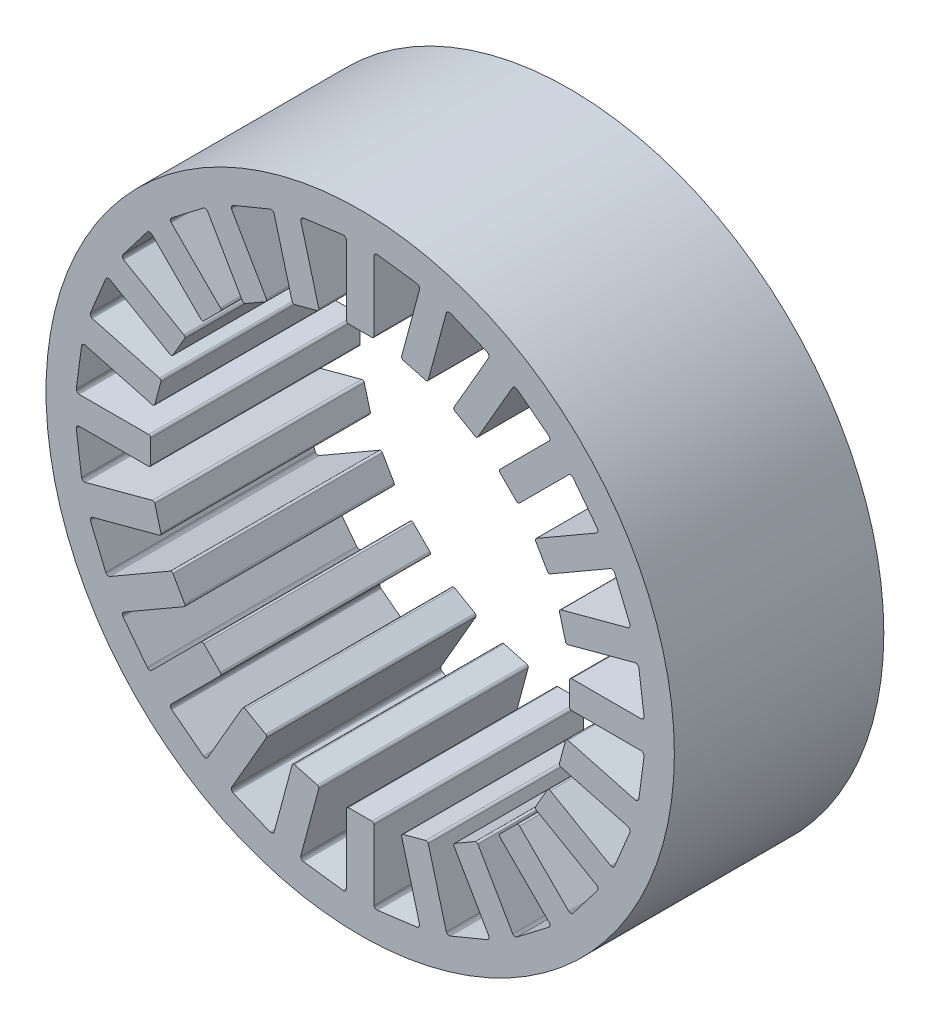
SolidWorks part; units mm, degrees
ref_plane "Ön Düzlem" through (0, 0, 0) normal (0, 0, 1) x (1, 0, 0)
ref_plane "Üst Düzlem" through (0, 0, 0) normal (0, 1, 0) x (1, 0, 0)
ref_plane "Sağ Düzlem" through (0, 0, 0) normal (1, 0, 0) x (0, 0, -1)
sketch "Model" plane through (0, 0, 0) normal (0, 0, 1) x (1, 0, 0)
  line L1 (60.5945, 121.4987) -> (60.8885, 121.3363)
  line L2 (60.8885, 121.3363) -> (61.139, 121.1124)
  line L3 (61.139, 121.1124) -> (61.3334, 120.8385)
  line L4 (61.3334, 120.8385) -> (61.4619, 120.5282)
  line L5 (61.4619, 120.5282) -> (61.5182, 120.197)
  line L6 (61.5182, 120.197) -> (61.4993, 119.8617)
  line L7 (61.4993, 119.8617) -> (61.4063, 119.5389)
  line L8 (61.4063, 119.5389) -> (45.7726, 92.4605)
  line L9 (45.7726, 92.4605) -> (42.0525, 92.3778)
  line L10 (42.0525, 92.3778) -> (41.4785, 90.992)
  line L11 (58.0621, 81.4174) -> (58.9753, 82.6074)
  line L12 (58.9753, 82.6074) -> (57.1868, 85.8705)
  line L13 (57.1868, 85.8705) -> (72.8206, 112.9489)
  line L14 (72.8206, 112.9489) -> (73.0536, 113.1908)
  line L15 (73.0536, 113.1908) -> (73.3346, 113.3748)
  line L16 (73.3346, 113.3748) -> (73.6495, 113.4917)
  line L17 (73.6495, 113.4917) -> (73.9825, 113.5355)
  line L18 (73.9825, 113.5355) -> (74.317, 113.5041)
  line L19 (74.317, 113.5041) -> (74.636, 113.3991)
  line L20 (74.636, 113.3991) -> (74.9237, 113.2258)
  line L21 (74.9237, 113.2258) -> (89.976, 101.6758)
  line L22 (89.976, 101.6758) -> (90.2179, 101.4427)
  line L23 (90.2179, 101.4427) -> (90.4019, 101.1617)
  line L24 (90.4019, 101.1617) -> (90.5188, 100.8468)
  line L25 (90.5188, 100.8468) -> (90.5626, 100.5138)
  line L26 (90.5626, 100.5138) -> (90.5313, 100.1793)
  line L27 (90.5313, 100.1793) -> (90.4263, 99.8603)
  line L28 (90.4263, 99.8603) -> (90.2529, 99.5726)
  line L29 (90.2529, 99.5726) -> (68.1435, 77.4631)
  line L30 (68.1435, 77.4631) -> (64.5287, 78.3461)
  line L31 (64.5287, 78.3461) -> (63.6156, 77.1561)
  line L32 (77.1561, 63.6156) -> (78.3461, 64.5287)
  line L33 (78.3461, 64.5287) -> (77.4631, 68.1435)
  line L34 (77.4631, 68.1435) -> (99.5726, 90.2529)
  line L35 (99.5726, 90.2529) -> (99.8603, 90.4263)
  line L36 (99.8603, 90.4263) -> (100.1793, 90.5313)
  line L37 (100.1793, 90.5313) -> (100.5138, 90.5626)
  line L38 (100.5138, 90.5626) -> (100.8468, 90.5188)
  line L39 (100.8468, 90.5188) -> (101.1617, 90.4019)
  line L40 (101.1617, 90.4019) -> (101.4427, 90.2179)
  line L41 (101.4427, 90.2179) -> (101.6758, 89.976)
  line L42 (101.6758, 89.976) -> (113.2258, 74.9237)
  line L43 (113.2258, 74.9237) -> (113.3991, 74.636)
  line L44 (113.3991, 74.636) -> (113.5041, 74.317)
  line L45 (113.5041, 74.317) -> (113.5355, 73.9825)
  line L46 (113.5355, 73.9825) -> (113.4917, 73.6495)
  line L47 (113.4917, 73.6495) -> (113.3748, 73.3346)
  line L48 (113.3748, 73.3346) -> (113.1908, 73.0536)
  line L49 (113.1908, 73.0536) -> (112.9489, 72.8206)
  line L50 (112.9489, 72.8206) -> (85.8705, 57.1868)
  line L51 (85.8705, 57.1868) -> (82.6074, 58.9753)
  line L52 (82.6074, 58.9753) -> (81.4174, 58.0621)
  line L53 (90.992, 41.4785) -> (92.3778, 42.0525)
  line L54 (92.3778, 42.0525) -> (92.4605, 45.7726)
  line L55 (92.4605, 45.7726) -> (119.5389, 61.4063)
  line L56 (119.5389, 61.4063) -> (119.8617, 61.4993)
  line L57 (119.8617, 61.4993) -> (120.197, 61.5182)
  line L58 (120.197, 61.5182) -> (120.5282, 61.4619)
  line L59 (120.5282, 61.4619) -> (120.8385, 61.3334)
  line L60 (120.8385, 61.3334) -> (121.1124, 61.139)
  line L61 (121.1124, 61.139) -> (121.3363, 60.8885)
  line L62 (121.3363, 60.8885) -> (121.4987, 60.5945)
  line L63 (121.4987, 60.5945) -> (128.7594, 43.0658)
  line L64 (128.7594, 43.0658) -> (128.8524, 42.743)
  line L65 (128.8524, 42.743) -> (128.8712, 42.4076)
  line L66 (128.8712, 42.4076) -> (128.815, 42.0765)
  line L67 (128.815, 42.0765) -> (128.6864, 41.7662)
  line L68 (128.6864, 41.7662) -> (128.492, 41.4922)
  line L69 (128.492, 41.4922) -> (128.2416, 41.2684)
  line L70 (128.2416, 41.2684) -> (127.9476, 41.1059)
  line L71 (127.9476, 41.1059) -> (97.7455, 33.0133)
  line L72 (97.7455, 33.0133) -> (95.0566, 35.5853)
  line L73 (95.0566, 35.5853) -> (93.6707, 35.0113)
  line L74 (98.6269, 16.5147) -> (100.1141, 16.7105)
  line L75 (100.1141, 16.7105) -> (101.1568, 20.2824)
  line L76 (101.1568, 20.2824) -> (131.3588, 28.375)
  line L77 (131.3588, 28.375) -> (131.6947, 28.3813)
  line L78 (131.6947, 28.3813) -> (132.0235, 28.3127)
  line L79 (132.0235, 28.3127) -> (132.3288, 28.1726)
  line L80 (132.3288, 28.1726) -> (132.5953, 27.9682)
  line L81 (132.5953, 27.9682) -> (132.8096, 27.7095)
  line L82 (132.8096, 27.7095) -> (132.9609, 27.4097)
  line L83 (132.9609, 27.4097) -> (133.0418, 27.0836)
  line L84 (133.0418, 27.0836) -> (135.5183, 8.273)
  line L85 (135.5183, 8.273) -> (135.5246, 7.9371)
  line L86 (135.5246, 7.9371) -> (135.4559, 7.6083)
  line L87 (135.4559, 7.6083) -> (135.3159, 7.303)
  line L88 (135.3159, 7.303) -> (135.1114, 7.0365)
  line L89 (135.1114, 7.0365) -> (134.8528, 6.8222)
  line L90 (134.8528, 6.8222) -> (134.5529, 6.6709)
  line L91 (134.5529, 6.6709) -> (134.2269, 6.59)
  line L92 (134.2269, 6.59) -> (102.9594, 6.59)
  line L93 (102.9594, 6.59) -> (101.0278, 9.7704)
  line L94 (101.0278, 9.7704) -> (99.5406, 9.5746)
  line L95 (99.5406, -9.5746) -> (101.0278, -9.7704)
  line L96 (101.0278, -9.7704) -> (102.9594, -6.59)
  line L97 (102.9594, -6.59) -> (134.2269, -6.59)
  line L98 (134.2269, -6.59) -> (134.5529, -6.6709)
  line L99 (134.5529, -6.6709) -> (134.8528, -6.8222)
  line L100 (134.8528, -6.8222) -> (135.1114, -7.0365)
  line L101 (135.1114, -7.0365) -> (135.3159, -7.303)
  line L102 (135.3159, -7.303) -> (135.4559, -7.6083)
  line L103 (135.4559, -7.6083) -> (135.5246, -7.9371)
  line L104 (135.5246, -7.9371) -> (135.5183, -8.273)
  line L105 (135.5183, -8.273) -> (133.0418, -27.0836)
  line L106 (133.0418, -27.0836) -> (132.9609, -27.4097)
  line L107 (132.9609, -27.4097) -> (132.8096, -27.7095)
  line L108 (132.8096, -27.7095) -> (132.5953, -27.9682)
  line L109 (132.5953, -27.9682) -> (132.3288, -28.1726)
  line L110 (132.3288, -28.1726) -> (132.0235, -28.3127)
  line L111 (132.0235, -28.3127) -> (131.6947, -28.3813)
  line L112 (131.6947, -28.3813) -> (131.3588, -28.375)
  line L113 (131.3588, -28.375) -> (101.1568, -20.2824)
  line L114 (101.1568, -20.2824) -> (100.1141, -16.7105)
  line L115 (100.1141, -16.7105) -> (98.6269, -16.5147)
  line L116 (93.6707, -35.0113) -> (95.0566, -35.5853)
  line L117 (95.0566, -35.5853) -> (97.7455, -33.0133)
  line L118 (97.7455, -33.0133) -> (127.9476, -41.1059)
  line L119 (127.9476, -41.1059) -> (128.2416, -41.2684)
  line L120 (128.2416, -41.2684) -> (128.492, -41.4922)
  line L121 (128.492, -41.4922) -> (128.6864, -41.7662)
  line L122 (128.6864, -41.7662) -> (128.815, -42.0765)
  line L123 (128.815, -42.0765) -> (128.8712, -42.4076)
  line L124 (128.8712, -42.4076) -> (128.8524, -42.743)
  line L125 (128.8524, -42.743) -> (128.7594, -43.0658)
  line L126 (128.7594, -43.0658) -> (121.4987, -60.5945)
  line L127 (121.4987, -60.5945) -> (121.3363, -60.8885)
  line L128 (121.3363, -60.8885) -> (121.1124, -61.139)
  line L129 (121.1124, -61.139) -> (120.8385, -61.3334)
  line L130 (120.8385, -61.3334) -> (120.5282, -61.4619)
  line L131 (120.5282, -61.4619) -> (120.197, -61.5182)
  line L132 (120.197, -61.5182) -> (119.8617, -61.4993)
  line L133 (119.8617, -61.4993) -> (119.5389, -61.4063)
  line L134 (119.5389, -61.4063) -> (92.4605, -45.7726)
  line L135 (92.4605, -45.7726) -> (92.3778, -42.0525)
  line L136 (92.3778, -42.0525) -> (90.992, -41.4785)
  line L137 (81.4174, -58.0621) -> (82.6074, -58.9753)
  line L138 (82.6074, -58.9753) -> (85.8705, -57.1868)
  line L139 (85.8705, -57.1868) -> (112.9489, -72.8206)
  line L140 (112.9489, -72.8206) -> (113.1908, -73.0536)
  line L141 (113.1908, -73.0536) -> (113.3748, -73.3346)
  line L142 (113.3748, -73.3346) -> (113.4917, -73.6495)
  line L143 (113.4917, -73.6495) -> (113.5355, -73.9825)
  line L144 (113.5355, -73.9825) -> (113.5041, -74.317)
  line L145 (113.5041, -74.317) -> (113.3991, -74.636)
  line L146 (113.3991, -74.636) -> (113.2258, -74.9237)
  line L147 (113.2258, -74.9237) -> (101.6758, -89.976)
  line L148 (101.6758, -89.976) -> (101.4427, -90.2179)
  line L149 (101.4427, -90.2179) -> (101.1617, -90.4019)
  line L150 (101.1617, -90.4019) -> (100.8468, -90.5188)
  line L151 (100.8468, -90.5188) -> (100.5138, -90.5626)
  line L152 (100.5138, -90.5626) -> (100.1793, -90.5313)
  line L153 (100.1793, -90.5313) -> (99.8603, -90.4263)
  line L154 (99.8603, -90.4263) -> (99.5726, -90.2529)
  line L155 (99.5726, -90.2529) -> (77.4631, -68.1435)
  line L156 (77.4631, -68.1435) -> (78.3461, -64.5287)
  line L157 (78.3461, -64.5287) -> (77.1561, -63.6156)
  line L158 (63.6156, -77.1561) -> (64.5287, -78.3461)
  line L159 (64.5287, -78.3461) -> (68.1435, -77.4631)
  line L160 (68.1435, -77.4631) -> (90.2529, -99.5726)
  line L161 (90.2529, -99.5726) -> (90.4263, -99.8603)
  line L162 (90.4263, -99.8603) -> (90.5313, -100.1793)
  line L163 (90.5313, -100.1793) -> (90.5626, -100.5138)
  line L164 (90.5626, -100.5138) -> (90.5188, -100.8468)
  line L165 (90.5188, -100.8468) -> (90.4019, -101.1617)
  line L166 (90.4019, -101.1617) -> (90.2179, -101.4427)
  line L167 (90.2179, -101.4427) -> (89.976, -101.6758)
  line L168 (89.976, -101.6758) -> (74.9237, -113.2258)
  line L169 (74.9237, -113.2258) -> (74.636, -113.3991)
  line L170 (74.636, -113.3991) -> (74.317, -113.5041)
  line L171 (74.317, -113.5041) -> (73.9825, -113.5355)
  line L172 (73.9825, -113.5355) -> (73.6495, -113.4917)
  line L173 (73.6495, -113.4917) -> (73.3346, -113.3748)
  line L174 (73.3346, -113.3748) -> (73.0536, -113.1908)
  line L175 (73.0536, -113.1908) -> (72.8206, -112.9489)
  line L176 (72.8206, -112.9489) -> (57.1868, -85.8705)
  line L177 (57.1868, -85.8705) -> (58.9753, -82.6074)
  line L178 (58.9753, -82.6074) -> (58.0621, -81.4174)
  line L179 (41.4785, -90.992) -> (42.0525, -92.3778)
  line L180 (42.0525, -92.3778) -> (45.7726, -92.4605)
  line L181 (45.7726, -92.4605) -> (61.4063, -119.5389)
  line L182 (61.4063, -119.5389) -> (61.4993, -119.8617)
  line L183 (61.4993, -119.8617) -> (61.5182, -120.197)
  line L184 (61.5182, -120.197) -> (61.4619, -120.5282)
  line L185 (61.4619, -120.5282) -> (61.3334, -120.8385)
  line L186 (61.3334, -120.8385) -> (61.139, -121.1124)
  line L187 (61.139, -121.1124) -> (60.8885, -121.3363)
  line L188 (60.8885, -121.3363) -> (60.5945, -121.4987)
  line L189 (60.5945, -121.4987) -> (43.0658, -128.7594)
  line L190 (43.0658, -128.7594) -> (42.743, -128.8524)
  line L191 (42.743, -128.8524) -> (42.4076, -128.8712)
  line L192 (42.4076, -128.8712) -> (42.0765, -128.815)
  line L193 (42.0765, -128.815) -> (41.7662, -128.6864)
  line L194 (41.7662, -128.6864) -> (41.4922, -128.492)
  line L195 (41.4922, -128.492) -> (41.2684, -128.2416)
  line L196 (41.2684, -128.2416) -> (41.1059, -127.9476)
  line L197 (41.1059, -127.9476) -> (33.0133, -97.7455)
  line L198 (33.0133, -97.7455) -> (35.5853, -95.0566)
  line L199 (35.5853, -95.0566) -> (35.0113, -93.6707)
  line L200 (16.5147, -98.6269) -> (16.7105, -100.1141)
  line L201 (16.7105, -100.1141) -> (20.2824, -101.1568)
  line L202 (20.2824, -101.1568) -> (28.375, -131.3588)
  line L203 (28.375, -131.3588) -> (28.3813, -131.6947)
  line L204 (28.3813, -131.6947) -> (28.3127, -132.0235)
  line L205 (28.3127, -132.0235) -> (28.1726, -132.3288)
  line L206 (28.1726, -132.3288) -> (27.9682, -132.5953)
  line L207 (27.9682, -132.5953) -> (27.7095, -132.8096)
  line L208 (27.7095, -132.8096) -> (27.4097, -132.9609)
  line L209 (27.4097, -132.9609) -> (27.0836, -133.0418)
  line L210 (27.0836, -133.0418) -> (8.273, -135.5183)
  line L211 (8.273, -135.5183) -> (7.9371, -135.5246)
  line L212 (7.9371, -135.5246) -> (7.6083, -135.4559)
  line L213 (7.6083, -135.4559) -> (7.303, -135.3159)
  line L214 (7.303, -135.3159) -> (7.0365, -135.1114)
  line L215 (7.0365, -135.1114) -> (6.8222, -134.8528)
  line L216 (6.8222, -134.8528) -> (6.6709, -134.5529)
  line L217 (6.6709, -134.5529) -> (6.59, -134.2269)
  line L218 (6.59, -134.2269) -> (6.59, -102.9594)
  line L219 (6.59, -102.9594) -> (9.7704, -101.0278)
  line L220 (9.7704, -101.0278) -> (9.5746, -99.5406)
  line L221 (-9.5746, -99.5406) -> (-9.7704, -101.0278)
  line L222 (-9.7704, -101.0278) -> (-6.59, -102.9594)
  line L223 (-6.59, -102.9594) -> (-6.59, -134.2269)
  line L224 (-6.59, -134.2269) -> (-6.6709, -134.5529)
  line L225 (-6.6709, -134.5529) -> (-6.8222, -134.8528)
  line L226 (-6.8222, -134.8528) -> (-7.0365, -135.1114)
  line L227 (-7.0365, -135.1114) -> (-7.303, -135.3159)
  line L228 (-7.303, -135.3159) -> (-7.6083, -135.4559)
  line L229 (-7.6083, -135.4559) -> (-7.9371, -135.5246)
  line L230 (-7.9371, -135.5246) -> (-8.273, -135.5183)
  line L231 (-8.273, -135.5183) -> (-27.0836, -133.0418)
  line L232 (-27.0836, -133.0418) -> (-27.4097, -132.9609)
  line L233 (-27.4097, -132.9609) -> (-27.7095, -132.8096)
  line L234 (-27.7095, -132.8096) -> (-27.9682, -132.5953)
  line L235 (-27.9682, -132.5953) -> (-28.1726, -132.3288)
  line L236 (-28.1726, -132.3288) -> (-28.3127, -132.0235)
  line L237 (-28.3127, -132.0235) -> (-28.3813, -131.6947)
  line L238 (-28.3813, -131.6947) -> (-28.375, -131.3588)
  line L239 (-28.375, -131.3588) -> (-20.2824, -101.1568)
  line L240 (-20.2824, -101.1568) -> (-16.7105, -100.1141)
  line L241 (-16.7105, -100.1141) -> (-16.5147, -98.6269)
  line L242 (-35.0113, -93.6707) -> (-35.5853, -95.0566)
  line L243 (-35.5853, -95.0566) -> (-33.0133, -97.7455)
  line L244 (-33.0133, -97.7455) -> (-41.1059, -127.9476)
  line L245 (-41.1059, -127.9476) -> (-41.2684, -128.2416)
  line L246 (-41.2684, -128.2416) -> (-41.4922, -128.492)
  line L247 (-41.4922, -128.492) -> (-41.7662, -128.6864)
  line L248 (-41.7662, -128.6864) -> (-42.0765, -128.815)
  line L249 (-42.0765, -128.815) -> (-42.4076, -128.8712)
  line L250 (-42.4076, -128.8712) -> (-42.743, -128.8524)
  line L251 (-42.743, -128.8524) -> (-43.0658, -128.7594)
  line L252 (-43.0658, -128.7594) -> (-60.5945, -121.4987)
  line L253 (-60.5945, -121.4987) -> (-60.8885, -121.3363)
  line L254 (-60.8885, -121.3363) -> (-61.139, -121.1124)
  line L255 (-61.139, -121.1124) -> (-61.3334, -120.8385)
  line L256 (-61.3334, -120.8385) -> (-61.4619, -120.5282)
  line L257 (-61.4619, -120.5282) -> (-61.5182, -120.197)
  line L258 (-61.5182, -120.197) -> (-61.4993, -119.8617)
  line L259 (-61.4993, -119.8617) -> (-61.4063, -119.5389)
  line L260 (-61.4063, -119.5389) -> (-45.7726, -92.4605)
  line L261 (-45.7726, -92.4605) -> (-42.0525, -92.3778)
  line L262 (-42.0525, -92.3778) -> (-41.4785, -90.992)
  line L263 (-58.0621, -81.4174) -> (-58.9753, -82.6074)
  line L264 (-58.9753, -82.6074) -> (-57.1868, -85.8705)
  line L265 (-57.1868, -85.8705) -> (-72.8206, -112.9489)
  line L266 (-72.8206, -112.9489) -> (-73.0536, -113.1908)
  line L267 (-73.0536, -113.1908) -> (-73.3346, -113.3748)
  line L268 (-73.3346, -113.3748) -> (-73.6495, -113.4917)
  line L269 (-73.6495, -113.4917) -> (-73.9825, -113.5355)
  line L270 (-73.9825, -113.5355) -> (-74.317, -113.5041)
  line L271 (-74.317, -113.5041) -> (-74.636, -113.3991)
  line L272 (-74.636, -113.3991) -> (-74.9237, -113.2258)
  line L273 (-74.9237, -113.2258) -> (-89.976, -101.6758)
  line L274 (-89.976, -101.6758) -> (-90.2179, -101.4427)
  line L275 (-90.2179, -101.4427) -> (-90.4019, -101.1617)
  line L276 (-90.4019, -101.1617) -> (-90.5188, -100.8468)
  line L277 (-90.5188, -100.8468) -> (-90.5626, -100.5138)
  line L278 (-90.5626, -100.5138) -> (-90.5313, -100.1793)
  line L279 (-90.5313, -100.1793) -> (-90.4263, -99.8603)
  line L280 (-90.4263, -99.8603) -> (-90.2529, -99.5726)
  line L281 (-90.2529, -99.5726) -> (-68.1435, -77.4631)
  line L282 (-68.1435, -77.4631) -> (-64.5287, -78.3461)
  line L283 (-64.5287, -78.3461) -> (-63.6156, -77.1561)
  line L284 (-77.1561, -63.6156) -> (-78.3461, -64.5287)
  line L285 (-78.3461, -64.5287) -> (-77.4631, -68.1435)
  line L286 (-77.4631, -68.1435) -> (-99.5726, -90.2529)
  line L287 (-99.5726, -90.2529) -> (-99.8603, -90.4263)
  line L288 (-99.8603, -90.4263) -> (-100.1793, -90.5313)
  line L289 (-100.1793, -90.5313) -> (-100.5138, -90.5626)
  line L290 (-100.5138, -90.5626) -> (-100.8468, -90.5188)
  line L291 (-100.8468, -90.5188) -> (-101.1617, -90.4019)
  line L292 (-101.1617, -90.4019) -> (-101.4427, -90.2179)
  line L293 (-101.4427, -90.2179) -> (-101.6758, -89.976)
  line L294 (-101.6758, -89.976) -> (-113.2258, -74.9237)
  line L295 (-113.2258, -74.9237) -> (-113.3991, -74.636)
  line L296 (-113.3991, -74.636) -> (-113.5041, -74.317)
  line L297 (-113.5041, -74.317) -> (-113.5355, -73.9825)
  line L298 (-113.5355, -73.9825) -> (-113.4917, -73.6495)
  line L299 (-113.4917, -73.6495) -> (-113.3748, -73.3346)
  line L300 (-113.3748, -73.3346) -> (-113.1908, -73.0536)
  line L301 (-113.1908, -73.0536) -> (-112.9489, -72.8206)
  line L302 (-112.9489, -72.8206) -> (-85.8705, -57.1868)
  line L303 (-85.8705, -57.1868) -> (-82.6074, -58.9753)
  line L304 (-82.6074, -58.9753) -> (-81.4174, -58.0621)
  line L305 (-90.992, -41.4785) -> (-92.3778, -42.0525)
  line L306 (-92.3778, -42.0525) -> (-92.4605, -45.7726)
  line L307 (-92.4605, -45.7726) -> (-119.5389, -61.4063)
  line L308 (-119.5389, -61.4063) -> (-119.8617, -61.4993)
  line L309 (-119.8617, -61.4993) -> (-120.197, -61.5182)
  line L310 (-120.197, -61.5182) -> (-120.5282, -61.4619)
  line L311 (-120.5282, -61.4619) -> (-120.8385, -61.3334)
  line L312 (-120.8385, -61.3334) -> (-121.1124, -61.139)
  line L313 (-121.1124, -61.139) -> (-121.3363, -60.8885)
  line L314 (-121.3363, -60.8885) -> (-121.4987, -60.5945)
  line L315 (-121.4987, -60.5945) -> (-128.7594, -43.0658)
  line L316 (-128.7594, -43.0658) -> (-128.8524, -42.743)
  line L317 (-128.8524, -42.743) -> (-128.8712, -42.4076)
  line L318 (-128.8712, -42.4076) -> (-128.815, -42.0765)
  line L319 (-128.815, -42.0765) -> (-128.6864, -41.7662)
  line L320 (-128.6864, -41.7662) -> (-128.492, -41.4922)
  line L321 (-128.492, -41.4922) -> (-128.2416, -41.2684)
  line L322 (-128.2416, -41.2684) -> (-127.9476, -41.1059)
  line L323 (-127.9476, -41.1059) -> (-97.7455, -33.0133)
  line L324 (-97.7455, -33.0133) -> (-95.0566, -35.5853)
  line L325 (-95.0566, -35.5853) -> (-93.6707, -35.0113)
  line L326 (-98.6269, -16.5147) -> (-100.1141, -16.7105)
  line L327 (-100.1141, -16.7105) -> (-101.1568, -20.2824)
  line L328 (-101.1568, -20.2824) -> (-131.3588, -28.375)
  line L329 (-131.3588, -28.375) -> (-131.6947, -28.3813)
  line L330 (-131.6947, -28.3813) -> (-132.0235, -28.3127)
  line L331 (-132.0235, -28.3127) -> (-132.3288, -28.1726)
  line L332 (-132.3288, -28.1726) -> (-132.5953, -27.9682)
  line L333 (-132.5953, -27.9682) -> (-132.8096, -27.7095)
  line L334 (-132.8096, -27.7095) -> (-132.9609, -27.4097)
  line L335 (-132.9609, -27.4097) -> (-133.0418, -27.0836)
  line L336 (-133.0418, -27.0836) -> (-135.5183, -8.273)
  line L337 (-135.5183, -8.273) -> (-135.5246, -7.9371)
  line L338 (-135.5246, -7.9371) -> (-135.4559, -7.6083)
  line L339 (-135.4559, -7.6083) -> (-135.3159, -7.303)
  line L340 (-135.3159, -7.303) -> (-135.1114, -7.0365)
  line L341 (-135.1114, -7.0365) -> (-134.8528, -6.8222)
  line L342 (-134.8528, -6.8222) -> (-134.5529, -6.6709)
  line L343 (-134.5529, -6.6709) -> (-134.2269, -6.59)
  line L344 (-134.2269, -6.59) -> (-102.9594, -6.59)
  line L345 (-102.9594, -6.59) -> (-101.0278, -9.7704)
  line L346 (-101.0278, -9.7704) -> (-99.5406, -9.5746)
  line L347 (-99.5406, 9.5746) -> (-101.0278, 9.7704)
  line L348 (-101.0278, 9.7704) -> (-102.9594, 6.59)
  line L349 (-102.9594, 6.59) -> (-134.2269, 6.59)
  line L350 (-134.2269, 6.59) -> (-134.5529, 6.6709)
  line L351 (-134.5529, 6.6709) -> (-134.8528, 6.8222)
  line L352 (-134.8528, 6.8222) -> (-135.1114, 7.0365)
  line L353 (-135.1114, 7.0365) -> (-135.3159, 7.303)
  line L354 (-135.3159, 7.303) -> (-135.4559, 7.6083)
  line L355 (-135.4559, 7.6083) -> (-135.5246, 7.9371)
  line L356 (-135.5246, 7.9371) -> (-135.5183, 8.273)
  line L357 (-135.5183, 8.273) -> (-133.0418, 27.0836)
  line L358 (-133.0418, 27.0836) -> (-132.9609, 27.4097)
  line L359 (-132.9609, 27.4097) -> (-132.8096, 27.7095)
  line L360 (-132.8096, 27.7095) -> (-132.5953, 27.9682)
  line L361 (-132.5953, 27.9682) -> (-132.3288, 28.1726)
  line L362 (-132.3288, 28.1726) -> (-132.0235, 28.3127)
  line L363 (-132.0235, 28.3127) -> (-131.6947, 28.3813)
  line L364 (-131.6947, 28.3813) -> (-131.3588, 28.375)
  line L365 (-131.3588, 28.375) -> (-101.1568, 20.2824)
  line L366 (-101.1568, 20.2824) -> (-100.1141, 16.7105)
  line L367 (-100.1141, 16.7105) -> (-98.6269, 16.5147)
  line L368 (-93.6707, 35.0113) -> (-95.0566, 35.5853)
  line L369 (-95.0566, 35.5853) -> (-97.7455, 33.0133)
  line L370 (-97.7455, 33.0133) -> (-127.9476, 41.1059)
  line L371 (-127.9476, 41.1059) -> (-128.2416, 41.2684)
  line L372 (-128.2416, 41.2684) -> (-128.492, 41.4922)
  line L373 (-128.492, 41.4922) -> (-128.6864, 41.7662)
  line L374 (-128.6864, 41.7662) -> (-128.815, 42.0765)
  line L375 (-128.815, 42.0765) -> (-128.8712, 42.4076)
  line L376 (-128.8712, 42.4076) -> (-128.8524, 42.743)
  line L377 (-128.8524, 42.743) -> (-128.7594, 43.0658)
  line L378 (-128.7594, 43.0658) -> (-121.4987, 60.5945)
  line L379 (-121.4987, 60.5945) -> (-121.3363, 60.8885)
  line L380 (-121.3363, 60.8885) -> (-121.1124, 61.139)
  line L381 (-121.1124, 61.139) -> (-120.8385, 61.3334)
  line L382 (-120.8385, 61.3334) -> (-120.5282, 61.4619)
  line L383 (-120.5282, 61.4619) -> (-120.197, 61.5182)
  line L384 (-120.197, 61.5182) -> (-119.8617, 61.4993)
  line L385 (-119.8617, 61.4993) -> (-119.5389, 61.4063)
  line L386 (-119.5389, 61.4063) -> (-92.4605, 45.7726)
  line L387 (-92.4605, 45.7726) -> (-92.3778, 42.0525)
  line L388 (-92.3778, 42.0525) -> (-90.992, 41.4785)
  line L389 (-81.4174, 58.0621) -> (-82.6074, 58.9753)
  line L390 (-82.6074, 58.9753) -> (-85.8705, 57.1868)
  line L391 (-85.8705, 57.1868) -> (-112.9489, 72.8206)
  line L392 (-112.9489, 72.8206) -> (-113.1908, 73.0536)
  line L393 (-113.1908, 73.0536) -> (-113.3748, 73.3346)
  line L394 (-113.3748, 73.3346) -> (-113.4917, 73.6495)
  line L395 (-113.4917, 73.6495) -> (-113.5355, 73.9825)
  line L396 (-113.5355, 73.9825) -> (-113.5041, 74.317)
  line L397 (-113.5041, 74.317) -> (-113.3991, 74.636)
  line L398 (-113.3991, 74.636) -> (-113.2258, 74.9237)
  line L399 (-113.2258, 74.9237) -> (-101.6758, 89.976)
  line L400 (-101.6758, 89.976) -> (-101.4427, 90.2179)
  line L401 (-101.4427, 90.2179) -> (-101.1617, 90.4019)
  line L402 (-101.1617, 90.4019) -> (-100.8468, 90.5188)
  line L403 (-100.8468, 90.5188) -> (-100.5138, 90.5626)
  line L404 (-100.5138, 90.5626) -> (-100.1793, 90.5313)
  line L405 (-100.1793, 90.5313) -> (-99.8603, 90.4263)
  line L406 (-99.8603, 90.4263) -> (-99.5726, 90.2529)
  line L407 (-99.5726, 90.2529) -> (-77.4631, 68.1435)
  line L408 (-77.4631, 68.1435) -> (-78.3461, 64.5287)
  line L409 (-78.3461, 64.5287) -> (-77.1561, 63.6156)
  line L410 (-63.6156, 77.1561) -> (-64.5287, 78.3461)
  line L411 (-64.5287, 78.3461) -> (-68.1435, 77.4631)
  line L412 (-68.1435, 77.4631) -> (-90.2529, 99.5726)
  line L413 (-90.2529, 99.5726) -> (-90.4263, 99.8603)
  line L414 (-90.4263, 99.8603) -> (-90.5313, 100.1793)
  line L415 (-90.5313, 100.1793) -> (-90.5626, 100.5138)
  line L416 (-90.5626, 100.5138) -> (-90.5188, 100.8468)
  line L417 (-90.5188, 100.8468) -> (-90.4019, 101.1617)
  line L418 (-90.4019, 101.1617) -> (-90.2179, 101.4427)
  line L419 (-90.2179, 101.4427) -> (-89.976, 101.6758)
  line L420 (-89.976, 101.6758) -> (-74.9237, 113.2258)
  line L421 (-74.9237, 113.2258) -> (-74.636, 113.3991)
  line L422 (-74.636, 113.3991) -> (-74.317, 113.5041)
  line L423 (-74.317, 113.5041) -> (-73.9825, 113.5355)
  line L424 (-73.9825, 113.5355) -> (-73.6495, 113.4917)
  line L425 (-73.6495, 113.4917) -> (-73.3346, 113.3748)
  line L426 (-73.3346, 113.3748) -> (-73.0536, 113.1908)
  line L427 (-73.0536, 113.1908) -> (-72.8206, 112.9489)
  line L428 (-72.8206, 112.9489) -> (-57.1868, 85.8705)
  line L429 (-57.1868, 85.8705) -> (-58.9753, 82.6074)
  line L430 (-58.9753, 82.6074) -> (-58.0621, 81.4174)
  line L431 (-41.4785, 90.992) -> (-42.0525, 92.3778)
  line L432 (-42.0525, 92.3778) -> (-45.7726, 92.4605)
  line L433 (-45.7726, 92.4605) -> (-61.4063, 119.5389)
  line L434 (-61.4063, 119.5389) -> (-61.4993, 119.8617)
  line L435 (-61.4993, 119.8617) -> (-61.5182, 120.197)
  line L436 (-61.5182, 120.197) -> (-61.4619, 120.5282)
  line L437 (-61.4619, 120.5282) -> (-61.3334, 120.8385)
  line L438 (-61.3334, 120.8385) -> (-61.139, 121.1124)
  line L439 (-61.139, 121.1124) -> (-60.8885, 121.3363)
  line L440 (-60.8885, 121.3363) -> (-60.5945, 121.4987)
  line L441 (-60.5945, 121.4987) -> (-43.0658, 128.7594)
  line L442 (-43.0658, 128.7594) -> (-42.743, 128.8524)
  line L443 (-42.743, 128.8524) -> (-42.4076, 128.8712)
  line L444 (-42.4076, 128.8712) -> (-42.0765, 128.815)
  line L445 (-42.0765, 128.815) -> (-41.7662, 128.6864)
  line L446 (-41.7662, 128.6864) -> (-41.4922, 128.492)
  line L447 (-41.4922, 128.492) -> (-41.2684, 128.2416)
  line L448 (-41.2684, 128.2416) -> (-41.1059, 127.9476)
  line L449 (-41.1059, 127.9476) -> (-33.0133, 97.7455)
  line L450 (-33.0133, 97.7455) -> (-35.5853, 95.0566)
  line L451 (-35.5853, 95.0566) -> (-35.0113, 93.6707)
  line L452 (-16.5147, 98.6269) -> (-16.7105, 100.1141)
  line L453 (-16.7105, 100.1141) -> (-20.2824, 101.1568)
  line L454 (-20.2824, 101.1568) -> (-28.375, 131.3588)
  line L455 (-28.375, 131.3588) -> (-28.3813, 131.6947)
  line L456 (-28.3813, 131.6947) -> (-28.3127, 132.0235)
  line L457 (-28.3127, 132.0235) -> (-28.1726, 132.3288)
  line L458 (-28.1726, 132.3288) -> (-27.9682, 132.5953)
  line L459 (-27.9682, 132.5953) -> (-27.7095, 132.8096)
  line L460 (-27.7095, 132.8096) -> (-27.4097, 132.9609)
  line L461 (-27.4097, 132.9609) -> (-27.0836, 133.0418)
  line L462 (-27.0836, 133.0418) -> (-8.273, 135.5183)
  line L463 (-8.273, 135.5183) -> (-7.9371, 135.5246)
  line L464 (-7.9371, 135.5246) -> (-7.6083, 135.4559)
  line L465 (-7.6083, 135.4559) -> (-7.303, 135.3159)
  line L466 (-7.303, 135.3159) -> (-7.0365, 135.1114)
  line L467 (-7.0365, 135.1114) -> (-6.8222, 134.8528)
  line L468 (-6.8222, 134.8528) -> (-6.6709, 134.5529)
  line L469 (-6.6709, 134.5529) -> (-6.59, 134.2269)
  line L470 (-6.59, 134.2269) -> (-6.59, 102.9594)
  line L471 (-6.59, 102.9594) -> (-9.7704, 101.0278)
  line L472 (-9.7704, 101.0278) -> (-9.5746, 99.5406)
  line L473 (9.5746, 99.5406) -> (9.7704, 101.0278)
  line L474 (9.7704, 101.0278) -> (6.59, 102.9594)
  line L475 (6.59, 102.9594) -> (6.59, 134.2269)
  line L476 (6.59, 134.2269) -> (6.6709, 134.5529)
  line L477 (6.6709, 134.5529) -> (6.8222, 134.8528)
  line L478 (6.8222, 134.8528) -> (7.0365, 135.1114)
  line L479 (7.0365, 135.1114) -> (7.303, 135.3159)
  line L480 (7.303, 135.3159) -> (7.6083, 135.4559)
  line L481 (7.6083, 135.4559) -> (7.9371, 135.5246)
  line L482 (7.9371, 135.5246) -> (8.273, 135.5183)
  line L483 (8.273, 135.5183) -> (27.0836, 133.0418)
  line L484 (27.0836, 133.0418) -> (27.4097, 132.9609)
  line L485 (27.4097, 132.9609) -> (27.7095, 132.8096)
  line L486 (27.7095, 132.8096) -> (27.9682, 132.5953)
  line L487 (27.9682, 132.5953) -> (28.1726, 132.3288)
  line L488 (28.1726, 132.3288) -> (28.3127, 132.0235)
  line L489 (28.3127, 132.0235) -> (28.3813, 131.6947)
  line L490 (28.3813, 131.6947) -> (28.375, 131.3588)
  line L491 (28.375, 131.3588) -> (20.2824, 101.1568)
  line L492 (20.2824, 101.1568) -> (16.7105, 100.1141)
  line L493 (16.7105, 100.1141) -> (16.5147, 98.6269)
  line L494 (35.0113, 93.6707) -> (35.5853, 95.0566)
  line L495 (35.5853, 95.0566) -> (33.0133, 97.7455)
  line L496 (33.0133, 97.7455) -> (41.1059, 127.9476)
  line L497 (41.1059, 127.9476) -> (41.2684, 128.2416)
  line L498 (41.2684, 128.2416) -> (41.4922, 128.492)
  line L499 (41.4922, 128.492) -> (41.7662, 128.6864)
  line L500 (41.7662, 128.6864) -> (42.0765, 128.815)
  line L501 (42.0765, 128.815) -> (42.4076, 128.8712)
  line L502 (42.4076, 128.8712) -> (42.743, 128.8524)
  line L503 (42.743, 128.8524) -> (43.0658, 128.7594)
  line L504 (43.0658, 128.7594) -> (60.5945, 121.4987)
  arc A0 (145, 0) -> (64.7137, 129.758) centre (0, 0) ccw
  arc A1 (58.0621, 81.4174) -> (41.4785, 90.992) centre (0, 0) ccw
  arc A2 (77.1561, 63.6156) -> (63.6156, 77.1561) centre (0, 0) ccw
  arc A3 (90.992, 41.4785) -> (81.4174, 58.0621) centre (0, 0) ccw
  arc A4 (98.6269, 16.5147) -> (93.6707, 35.0113) centre (0, 0) ccw
  arc A5 (99.5406, -9.5746) -> (99.5406, 9.5746) centre (0, 0) ccw
  arc A6 (93.6707, -35.0113) -> (98.6269, -16.5147) centre (0, 0) ccw
  arc A7 (81.4174, -58.0621) -> (90.992, -41.4785) centre (0, 0) ccw
  arc A8 (63.6156, -77.1561) -> (77.1561, -63.6156) centre (0, 0) ccw
  arc A9 (41.4785, -90.992) -> (58.0621, -81.4174) centre (0, 0) ccw
  arc A10 (16.5147, -98.6269) -> (35.0113, -93.6707) centre (0, 0) ccw
  arc A11 (-9.5746, -99.5406) -> (9.5746, -99.5406) centre (0, 0) ccw
  arc A12 (-35.0113, -93.6707) -> (-16.5147, -98.6269) centre (0, 0) ccw
  arc A13 (-58.0621, -81.4174) -> (-41.4785, -90.992) centre (0, 0) ccw
  arc A14 (-77.1561, -63.6156) -> (-63.6156, -77.1561) centre (0, 0) ccw
  arc A15 (-90.992, -41.4785) -> (-81.4174, -58.0621) centre (0, 0) ccw
  arc A16 (-98.6269, -16.5147) -> (-93.6707, -35.0113) centre (0, 0) ccw
  arc A17 (-99.5406, 9.5746) -> (-99.5406, -9.5746) centre (0, 0) ccw
  arc A18 (-93.6707, 35.0113) -> (-98.6269, 16.5147) centre (0, 0) ccw
  arc A19 (-81.4174, 58.0621) -> (-90.992, 41.4785) centre (0, 0) ccw
  arc A20 (-63.6156, 77.1561) -> (-77.1561, 63.6156) centre (0, 0) ccw
  arc A21 (-41.4785, 90.992) -> (-58.0621, 81.4174) centre (0, 0) ccw
  arc A22 (-16.5147, 98.6269) -> (-35.0113, 93.6707) centre (0, 0) ccw
  arc A23 (9.5746, 99.5406) -> (-9.5746, 99.5406) centre (0, 0) ccw
  arc A24 (35.0113, 93.6707) -> (16.5147, 98.6269) centre (0, 0) ccw
  arc A25 (64.7137, 129.758) -> (145, 0) centre (0, 0) ccw
extrude "Yükseklik-Ekstrüzyon1" add sketch "Model" along normal blind 100
sketch "Çizim1" plane through (0, 0, 100) normal (0, 0, 1) x (1, 0, 0)
  circle A0 centre (0, 0) radius 148
  circle A1 centre (0, 0) radius 145
  dimension "D1" = 296
extrude "Yükseklik-Ekstrüzyon2" add sketch "Çizim1" against normal up to surface (100 mm away) up to face at (145, 0, 0)
sketch "Çizim2" plane through (0, 0, 100) normal (0, 0, 1) x (1, 0, 0)
  line L1 (0, 156) -> (0, 182.2267) construction
  arc A0 (-3.9597, 147.947) -> (3.9597, 147.947) centre (0, 151) ccw
  circle A2 centre (0, 0) radius 148 construction
  arc A3 (3.9597, 147.947) -> (-3.9597, 147.947) centre (0, 0) ccw
  dimension "D1" = 10
  dimension "D2" = 2
extrude "Kes-Ekstrüzyon1" cut sketch "Çizim2" against normal up to surface (100 mm away) up to face at (0, 0, 0)
pattern_circular "Dairesel Kaplama1" count 6 over 360 about axis through (0, 0, 0) along (0, 0, -1) of "Kes-Ekstrüzyon1"
sketch "Sketch1" plane through (0, 0, 100) normal (0, 0, 1) x (1, 0, 0)
  circle A0 centre (0, 0) radius 150
  circle A1 centre (1.9909, 0) radius 143.5301
extrude "Boss-Extrude4" add sketch "Sketch1" against normal blind 100
sketch "Sketch2" plane through (0, 0, 100) normal (0, 0, 1) x (1, 0, 0)
  circle A0 centre (0, 0) radius 103.1701
extrude "Cut-Extrude1" cut sketch "Sketch2" against normal blind 100
sketch "Sketch3" plane through (0, 0, 100) normal (0, 0, 1) x (1, 0, 0)
sketch "Sketch4" plane through (0, 0, 100) normal (0, 0, 1) x (1, 0, 0)
  line L0 (21.1574, 104.4224) -> (19.7753, 99.2641)
  line L1 (-6.59, 106.3402) -> (6.59, 106.3402)
  line L2 (-6.59, 106.3402) -> (-6.59, 101)
  line L3 (-5.59, 100) -> (5.59, 100)
  line L4 (6.59, 106.3402) -> (6.59, 101)
  line L5 (-6.59, 106.3402) -> (6.59, 100) construction
  line L6 (-6.59, 100) -> (6.59, 106.3402) construction
  line L7 (21.1574, 104.4224) -> (33.8883, 101.0111)
  line L8 (33.8883, 101.0111) -> (32.5062, 95.8529)
  line L9 (20.4824, 98.0394) -> (31.2814, 95.1458)
  line L10 (47.463, 95.3883) -> (44.7929, 90.7636)
  line L11 (47.463, 95.3883) -> (58.8772, 88.7983)
  line L12 (58.8772, 88.7983) -> (56.2071, 84.1736)
  line L13 (45.1589, 89.3975) -> (54.8411, 83.8075)
  line L14 (70.534, 79.8537) -> (66.758, 76.0776)
  line L15 (70.534, 79.8537) -> (79.8537, 70.534)
  line L16 (79.8537, 70.534) -> (76.0776, 66.758)
  line L17 (66.758, 74.6634) -> (74.6634, 66.758)
  line L18 (88.7983, 58.8772) -> (84.1736, 56.2071)
  line L19 (88.7983, 58.8772) -> (95.3883, 47.463)
  line L20 (95.3883, 47.463) -> (90.7636, 44.7929)
  line L21 (83.8075, 54.8411) -> (89.3975, 45.1589)
  line L22 (101.0111, 33.8883) -> (95.8529, 32.5062)
  line L23 (101.0111, 33.8883) -> (104.4224, 21.1574)
  line L24 (104.4224, 21.1574) -> (99.2641, 19.7753)
  line L25 (95.1458, 31.2814) -> (98.0394, 20.4824)
  line L26 (106.3402, 6.59) -> (101, 6.59)
  line L27 (106.3402, 6.59) -> (106.3402, -6.59)
  line L28 (106.3402, -6.59) -> (101, -6.59)
  line L29 (100, 5.59) -> (100, -5.59)
  line L30 (104.4224, -21.1574) -> (99.2641, -19.7753)
  line L31 (104.4224, -21.1574) -> (101.0111, -33.8883)
  line L32 (101.0111, -33.8883) -> (95.8529, -32.5062)
  line L33 (98.0394, -20.4824) -> (95.1458, -31.2814)
  line L34 (95.3883, -47.463) -> (90.7636, -44.7929)
  line L35 (95.3883, -47.463) -> (88.7983, -58.8772)
  line L36 (88.7983, -58.8772) -> (84.1736, -56.2071)
  line L37 (89.3975, -45.1589) -> (83.8075, -54.8411)
  line L38 (79.8537, -70.534) -> (76.0776, -66.758)
  line L39 (79.8537, -70.534) -> (70.534, -79.8537)
  line L40 (70.534, -79.8537) -> (66.758, -76.0776)
  line L41 (74.6634, -66.758) -> (66.758, -74.6634)
  line L42 (58.8772, -88.7983) -> (56.2071, -84.1736)
  line L43 (58.8772, -88.7983) -> (47.463, -95.3883)
  line L44 (47.463, -95.3883) -> (44.7929, -90.7636)
  line L45 (54.8411, -83.8075) -> (45.1589, -89.3975)
  line L46 (33.8883, -101.0111) -> (32.5062, -95.8529)
  line L47 (33.8883, -101.0111) -> (21.1574, -104.4224)
  line L48 (21.1574, -104.4224) -> (19.7753, -99.2641)
  line L49 (31.2814, -95.1458) -> (20.4824, -98.0394)
  line L50 (6.59, -106.3402) -> (6.59, -101)
  line L51 (6.59, -106.3402) -> (-6.59, -106.3402)
  line L52 (-6.59, -106.3402) -> (-6.59, -101)
  line L53 (5.59, -100) -> (-5.59, -100)
  line L54 (-21.1574, -104.4224) -> (-19.7753, -99.2641)
  line L55 (-21.1574, -104.4224) -> (-33.8883, -101.0111)
  line L56 (-33.8883, -101.0111) -> (-32.5062, -95.8529)
  line L57 (-20.4824, -98.0394) -> (-31.2814, -95.1458)
  line L58 (-47.463, -95.3883) -> (-44.7929, -90.7636)
  line L59 (-47.463, -95.3883) -> (-58.8772, -88.7983)
  line L60 (-58.8772, -88.7983) -> (-56.2071, -84.1736)
  line L61 (-45.1589, -89.3975) -> (-54.8411, -83.8075)
  line L62 (-70.534, -79.8537) -> (-66.758, -76.0776)
  line L63 (-70.534, -79.8537) -> (-79.8537, -70.534)
  line L64 (-79.8537, -70.534) -> (-76.0776, -66.758)
  line L65 (-66.758, -74.6634) -> (-74.6634, -66.758)
  line L66 (-88.7983, -58.8772) -> (-84.1736, -56.2071)
  line L67 (-88.7983, -58.8772) -> (-95.3883, -47.463)
  line L68 (-95.3883, -47.463) -> (-90.7636, -44.7929)
  line L69 (-83.8075, -54.8411) -> (-89.3975, -45.1589)
  line L70 (-101.0111, -33.8883) -> (-95.8529, -32.5062)
  line L71 (-101.0111, -33.8883) -> (-104.4224, -21.1574)
  line L72 (-104.4224, -21.1574) -> (-99.2641, -19.7753)
  line L73 (-95.1458, -31.2814) -> (-98.0394, -20.4824)
  line L74 (-106.3402, -6.59) -> (-101, -6.59)
  line L75 (-106.3402, -6.59) -> (-106.3402, 6.59)
  line L76 (-106.3402, 6.59) -> (-101, 6.59)
  line L77 (-100, -5.59) -> (-100, 5.59)
  line L78 (-104.4224, 21.1574) -> (-99.2641, 19.7753)
  line L79 (-104.4224, 21.1574) -> (-101.0111, 33.8883)
  line L80 (-101.0111, 33.8883) -> (-95.8529, 32.5062)
  line L81 (-98.0394, 20.4824) -> (-95.1458, 31.2814)
  line L82 (-95.3883, 47.463) -> (-90.7636, 44.7929)
  line L83 (-95.3883, 47.463) -> (-88.7983, 58.8772)
  line L84 (-88.7983, 58.8772) -> (-84.1736, 56.2071)
  line L85 (-89.3975, 45.1589) -> (-83.8075, 54.8411)
  line L86 (-79.8537, 70.534) -> (-76.0776, 66.758)
  line L87 (-79.8537, 70.534) -> (-70.534, 79.8537)
  line L88 (-70.534, 79.8537) -> (-66.758, 76.0776)
  line L89 (-74.6634, 66.758) -> (-66.758, 74.6634)
  line L90 (-58.8772, 88.7983) -> (-56.2071, 84.1736)
  line L91 (-58.8772, 88.7983) -> (-47.463, 95.3883)
  line L92 (-47.463, 95.3883) -> (-44.7929, 90.7636)
  line L93 (-54.8411, 83.8075) -> (-45.1589, 89.3975)
  line L94 (-33.8883, 101.0111) -> (-32.5062, 95.8529)
  line L95 (-33.8883, 101.0111) -> (-21.1574, 104.4224)
  line L96 (-21.1574, 104.4224) -> (-19.7753, 99.2641)
  line L97 (-31.2814, 95.1458) -> (-20.4824, 98.0394)
  arc A0 (6.59, 102.9594) -> (-6.59, 102.9594) centre (0, 0) ccw construction
  arc A1 (5.59, 100) -> (6.59, 101) centre (5.59, 101) ccw
  arc A2 (-5.59, 100) -> (-6.59, 101) centre (-5.59, 101) cw
  arc A3 (20.4824, 98.0394) -> (19.7753, 99.2641) centre (20.7412, 99.0053) cw
  arc A4 (31.2814, 95.1458) -> (32.5062, 95.8529) centre (31.5402, 96.1117) ccw
  arc A5 (45.1589, 89.3975) -> (44.7929, 90.7636) centre (45.6589, 90.2636) cw
  arc A6 (54.8411, 83.8075) -> (56.2071, 84.1736) centre (55.3411, 84.6736) ccw
  arc A7 (66.758, 74.6634) -> (66.758, 76.0776) centre (67.4651, 75.3705) cw
  arc A8 (74.6634, 66.758) -> (76.0776, 66.758) centre (75.3705, 67.4651) ccw
  arc A9 (83.8075, 54.8411) -> (84.1736, 56.2071) centre (84.6736, 55.3411) cw
  arc A10 (89.3975, 45.1589) -> (90.7636, 44.7929) centre (90.2636, 45.6589) ccw
  arc A11 (95.1458, 31.2814) -> (95.8529, 32.5062) centre (96.1117, 31.5402) cw
  arc A12 (98.0394, 20.4824) -> (99.2641, 19.7753) centre (99.0053, 20.7412) ccw
  arc A13 (100, 5.59) -> (101, 6.59) centre (101, 5.59) cw
  arc A14 (100, -5.59) -> (101, -6.59) centre (101, -5.59) ccw
  arc A15 (98.0394, -20.4824) -> (99.2641, -19.7753) centre (99.0053, -20.7412) cw
  arc A16 (95.1458, -31.2814) -> (95.8529, -32.5062) centre (96.1117, -31.5402) ccw
  arc A17 (89.3975, -45.1589) -> (90.7636, -44.7929) centre (90.2636, -45.6589) cw
  arc A18 (83.8075, -54.8411) -> (84.1736, -56.2071) centre (84.6736, -55.3411) ccw
  arc A19 (74.6634, -66.758) -> (76.0776, -66.758) centre (75.3705, -67.4651) cw
  arc A20 (66.758, -74.6634) -> (66.758, -76.0776) centre (67.4651, -75.3705) ccw
  arc A21 (54.8411, -83.8075) -> (56.2071, -84.1736) centre (55.3411, -84.6736) cw
  arc A22 (45.1589, -89.3975) -> (44.7929, -90.7636) centre (45.6589, -90.2636) ccw
  arc A23 (31.2814, -95.1458) -> (32.5062, -95.8529) centre (31.5402, -96.1117) cw
  arc A24 (20.4824, -98.0394) -> (19.7753, -99.2641) centre (20.7412, -99.0053) ccw
  arc A25 (5.59, -100) -> (6.59, -101) centre (5.59, -101) cw
  arc A26 (-5.59, -100) -> (-6.59, -101) centre (-5.59, -101) ccw
  arc A27 (-20.4824, -98.0394) -> (-19.7753, -99.2641) centre (-20.7412, -99.0053) cw
  arc A28 (-31.2814, -95.1458) -> (-32.5062, -95.8529) centre (-31.5402, -96.1117) ccw
  arc A29 (-45.1589, -89.3975) -> (-44.7929, -90.7636) centre (-45.6589, -90.2636) cw
  arc A30 (-54.8411, -83.8075) -> (-56.2071, -84.1736) centre (-55.3411, -84.6736) ccw
  arc A31 (-66.758, -74.6634) -> (-66.758, -76.0776) centre (-67.4651, -75.3705) cw
  arc A32 (-74.6634, -66.758) -> (-76.0776, -66.758) centre (-75.3705, -67.4651) ccw
  arc A33 (-83.8075, -54.8411) -> (-84.1736, -56.2071) centre (-84.6736, -55.3411) cw
  arc A34 (-89.3975, -45.1589) -> (-90.7636, -44.7929) centre (-90.2636, -45.6589) ccw
  arc A35 (-95.1458, -31.2814) -> (-95.8529, -32.5062) centre (-96.1117, -31.5402) cw
  arc A36 (-98.0394, -20.4824) -> (-99.2641, -19.7753) centre (-99.0053, -20.7412) ccw
  arc A37 (-100, -5.59) -> (-101, -6.59) centre (-101, -5.59) cw
  arc A38 (-100, 5.59) -> (-101, 6.59) centre (-101, 5.59) ccw
  arc A39 (-98.0394, 20.4824) -> (-99.2641, 19.7753) centre (-99.0053, 20.7412) cw
  arc A40 (-95.1458, 31.2814) -> (-95.8529, 32.5062) centre (-96.1117, 31.5402) ccw
  arc A41 (-89.3975, 45.1589) -> (-90.7636, 44.7929) centre (-90.2636, 45.6589) cw
  arc A42 (-83.8075, 54.8411) -> (-84.1736, 56.2071) centre (-84.6736, 55.3411) ccw
  arc A43 (-74.6634, 66.758) -> (-76.0776, 66.758) centre (-75.3705, 67.4651) cw
  arc A44 (-66.758, 74.6634) -> (-66.758, 76.0776) centre (-67.4651, 75.3705) ccw
  arc A45 (-54.8411, 83.8075) -> (-56.2071, 84.1736) centre (-55.3411, 84.6736) cw
  arc A46 (-45.1589, 89.3975) -> (-44.7929, 90.7636) centre (-45.6589, 90.2636) ccw
  arc A47 (-31.2814, 95.1458) -> (-32.5062, 95.8529) centre (-31.5402, 96.1117) cw
  arc A48 (-20.4824, 98.0394) -> (-19.7753, 99.2641) centre (-20.7412, 99.0053) ccw
  point P0 (0, 103.1701)
  point P201 (0, 0)
  dimension "D1" = 1
  dimension "D2" = 24
extrude "Boss-Extrude8" add sketch "Sketch4" against normal blind 100
